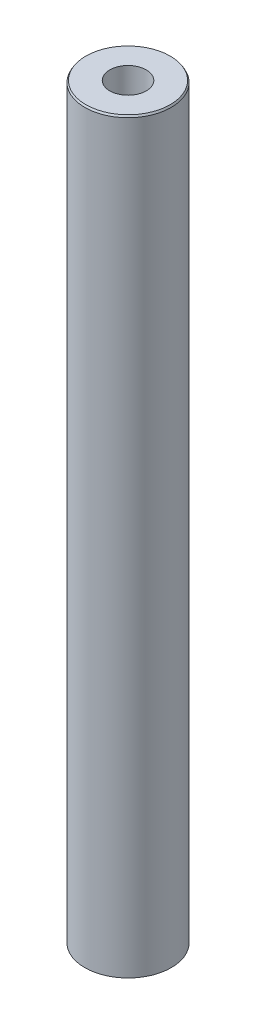
SolidWorks part; units mm, degrees
ref_plane "Front Plane" through (0, 0, 0) normal (0, 0, 1) x (1, 0, 0)
ref_plane "Top Plane" through (0, 0, 0) normal (0, 1, 0) x (1, 0, 0)
ref_plane "Right Plane" through (0, 0, 0) normal (1, 0, 0) x (0, 0, -1)
sketch "Sketch1" plane through (0, 0, 0) normal (0, 1, 0) x (1, 0, 0)
  circle A0 centre (0, 0) radius 5
  dimension "SHAFT_OD" = 10
extrude "Boss-Extrude1" add sketch "Sketch1" along normal blind 86.5352
sketch "Sketch2" plane through (0, 0, 0) normal (0, 1, 0) x (1, 0, 0)
  circle A0 centre (0, 0) radius 2.111
  dimension "BORE_D" = 4.2221
extrude "Cut-Extrude1" cut sketch "Sketch2" along normal through all
chamfer "Chamfer1" distance 0.212 angle 30 2 edges at (0, 86.5352, 5) (0, 0, 5) first distance on face at (0, 86.5352, 5) first distance on face at (0, 0, 2.111)
